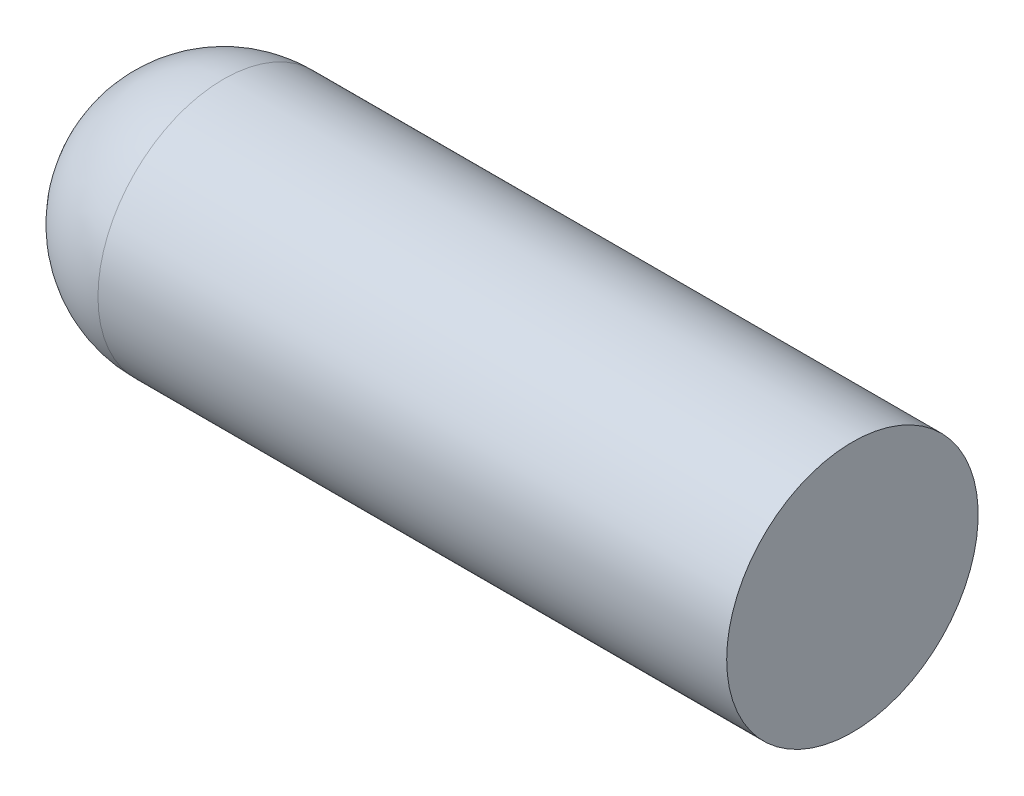
SolidWorks part; units mm, degrees
ref_plane "Front Plane" through (0, 0, 0) normal (0, 0, 1) x (1, 0, 0)
ref_plane "Top Plane" through (0, 0, 0) normal (0, 1, 0) x (1, 0, 0)
ref_plane "Right Plane" through (0, 0, 0) normal (1, 0, 0) x (0, 0, -1)
sketch "Sketch8" plane through (0, 0, 0) normal (0, 0, 1) x (1, 0, 0)
  line L10 (508, 0) -> (0, 0)
  line L12 (508, 78.359) -> (762, 78.359)
  line L14 (508, 0) -> (762, 0)
  line L16 (762, 0) -> (1524, 0)
  line L17 (762, 78.359) -> (1524, 78.359)
  line L18 (1524, 0) -> (1524, 78.359)
  spline S0 degree 4 poles (0, 0) (0.0028, 0.0112) (0.0101, 0.033) (0.0315, 0.074) (0.0698, 0.1316) (0.1192, 0.1954) (0.1898, 0.2761) (0.2748, 0.3639) (0.4019, 0.4843) (0.6026, 0.6567) (0.9144, 0.8984) (1.4448, 1.2671) (2.3422, 1.8219) (3.9262, 2.6864) (6.7922, 4.0534) (11.8911, 6.1625) (20.4311, 9.2161) (31.8916, 12.777) (45.6257, 16.595) (64.7152, 21.4391) (87.8428, 26.7555) (115.2609, 32.4758) (146.9821, 38.4855) (178.7896, 44.0179) (210.6663, 49.1356) (242.6009, 53.8775) (274.5859, 58.2664) (306.6159, 62.3133) (338.6872, 66.0193) (370.7971, 69.3748) (402.9439, 72.3578) (431.1037, 74.6062) (455.263, 76.2292) (474.4437, 77.278) (487.1031, 77.8359) (497.2672, 78.1744) (503.3998, 78.31) (506.4665, 78.3534) (508, 78.359) knots 0 0 0 0 0 0.000089 0.000179 0.000357 0.000536 0.000714 0.001009 0.001304 0.001892 0.002764 0.004066 0.006308 0.010067 0.016745 0.028668 0.049063 0.080344 0.109747 0.139151 0.201713 0.264275 0.326836 0.389398 0.45196 0.514521 0.577083 0.639645 0.702206 0.764768 0.82733 0.889891 0.921172 0.952453 0.976227 0.988113 1 1 1 1 1 construction
  spline S1 degree 4 poles (0, 0) (0.0028, 0.0112) (0.0101, 0.033) (0.0315, 0.074) (0.0698, 0.1316) (0.1192, 0.1954) (0.1898, 0.2761) (0.2748, 0.3639) (0.4019, 0.4843) (0.6026, 0.6567) (0.9144, 0.8984) (1.4448, 1.2671) (2.3422, 1.8219) (3.9262, 2.6864) (6.7922, 4.0534) (11.8911, 6.1625) (20.4311, 9.2161) (31.8916, 12.777) (45.6257, 16.595) (64.7152, 21.4391) (87.8428, 26.7555) (115.2609, 32.4758) (146.9821, 38.4855) (178.7896, 44.0179) (210.6663, 49.1356) (242.6009, 53.8775) (274.5859, 58.2664) (306.6159, 62.3133) (338.6872, 66.0193) (370.7971, 69.3748) (402.9439, 72.3578) (431.1037, 74.6062) (455.263, 76.2292) (474.4437, 77.278) (487.1031, 77.8359) (497.2672, 78.1744) (503.3998, 78.31) (506.4665, 78.3534) (508, 78.359) knots 0 0 0 0 0 0.000089 0.000179 0.000357 0.000536 0.000714 0.001009 0.001304 0.001892 0.002764 0.004066 0.006308 0.010067 0.016745 0.028668 0.049063 0.080344 0.109747 0.139151 0.201713 0.264275 0.326836 0.389398 0.45196 0.514521 0.577083 0.639645 0.702206 0.764768 0.82733 0.889891 0.921172 0.952453 0.976227 0.988113 1 1 1 1 1
  dimension "D1" = 78.359
  dimension "D2" = 254
  dimension "D3" = 78.359
  dimension "D4" = 508
  dimension "D5" = 78.359
  dimension "D6" = 762
revolve "Revolve8" add sketch "Sketch8" angle 360 about L10
sketch "Sketch9" plane through (0, 0, 0) normal (0, 0, 1) x (1, 0, 0)
  line L0 (-1524, 0) -> (7620.0001, 0)
  line L3 (0.0001, 1524) -> (7620.0001, 1524)
  line L4 (7620.0001, 0) -> (7620.0001, 1524)
  line L5 (0.0001, 1524) -> (0, 0) construction
  arc A0 (0.0001, 1524) -> (-1524, 0) centre (0, 0) ccw
  dimension "D1" = 1524
  dimension "D2" = 7620
revolve "Revolve9" add sketch "Sketch9" angle 360 about L0
combine bodies "Combine1" operation type subtract main body 110 bodies to subtract 108
curve "Curve1"
sketch "Sketch9<3>" plane through (0, 0, 0) normal (0, 0, 1) x (1, 0, 0) same geometry as "Sketch9"
